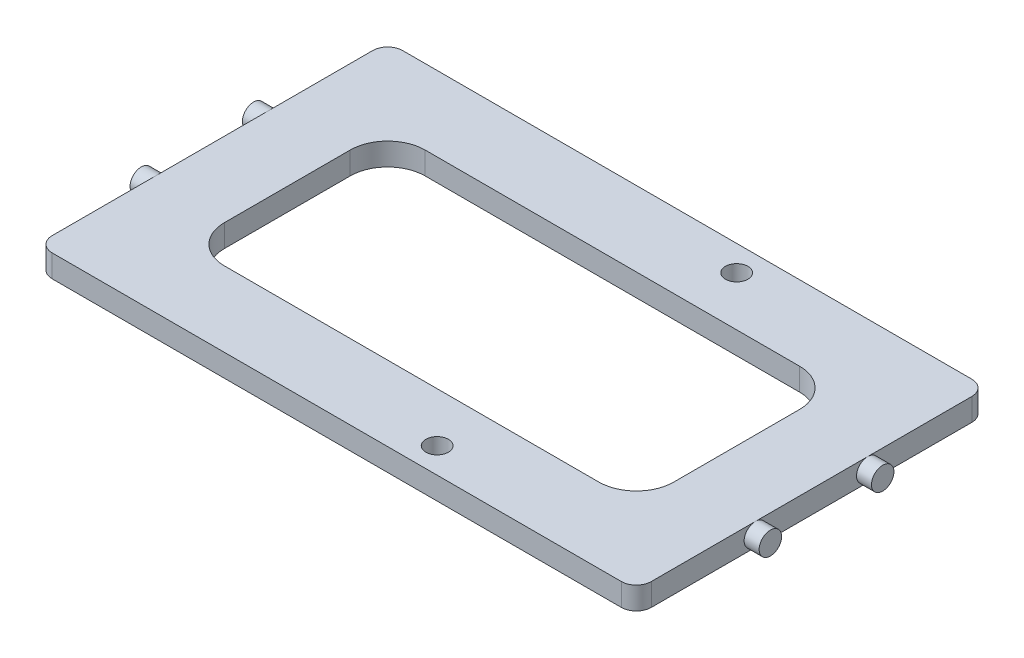
SolidWorks part; units mm, degrees
material "Copper"
ref_plane "Front Plane" through (0, 0, 0) normal (0, 0, 1) x (1, 0, 0)
ref_plane "Top Plane" through (0, 0, 0) normal (0, 1, 0) x (1, 0, 0)
ref_plane "Right Plane" through (0, 0, 0) normal (1, 0, 0) x (0, 0, -1)
sketch "Sketch1" plane through (0, 0, 0) normal (0, 1, 0) x (1, 0, 0)
  line L1 (0, 0) -> (101.6, 0)
  line L2 (0, 0) -> (0, 59.436)
  line L3 (0, 59.436) -> (101.6, 59.436)
  line L4 (101.6, 0) -> (101.6, 59.436)
  dimension "D1" = 59.436
  dimension "D2" = 101.6
extrude "Base Extrude" add sketch "Sketch1" along normal blind 3.81
fillet "Base Corner Fillet" radius 2.54 4 edges at (0, 1.905, 0) (0, 1.905, -59.436) (101.6, 1.905, -59.436) (101.6, 1.905, 0)
sketch "Sketch3" plane through (0, 0, 0) normal (-1, 0, 0) x (0, 0, 1)
  line L0 (-29.718, 3.81) -> (-29.718, 0) construction
  line L1 (-56.896, 3.81) -> (-2.54, 3.81) construction
  line L2 (-56.896, 0) -> (-2.54, 0) construction
  line L3 (0, 1.905) -> (-59.436, 1.905) construction
  line L4 (0, 3.81) -> (0, 0) construction
  line L5 (-59.436, 0) -> (-59.436, 3.81) construction
  circle A0 centre (-20.193, 1.905) radius 1.905
  circle A1 centre (-39.243, 1.905) radius 1.905
  dimension "D1" = 3.81
  dimension "D2" = 9.525
extrude "Peg Extrude" add sketch "Sketch3" along normal blind 2.54
ref_plane "Peg Mirror Plane" through (50.8, 0, 0) normal (1, 0, 0) x (0, 0, -1)
mirror "Peg Mirror" about plane through (50.8, 0, 0) normal (1, 0, 0) of "Peg Extrude"
sketch "Sketch4" plane through (0, 0, 0) normal (0, -1, 0) x (1, 0, 0)
  line L0 (2.54, 0) -> (99.06, 0) construction
  line L1 (19.05, -12.7) -> (82.55, -12.7)
  line L2 (12.7, -19.05) -> (12.7, -40.386)
  line L3 (19.05, -46.736) -> (82.55, -46.736)
  line L4 (88.9, -19.05) -> (88.9, -40.386)
  line L5 (99.06, -59.436) -> (2.54, -59.436) construction
  line L6 (0, -39.243) -> (0, -20.193) construction
  line L7 (101.6, -20.193) -> (101.6, -39.243) construction
  arc A0 (82.55, -12.7) -> (88.9, -19.05) centre (82.55, -19.05) cw
  arc A1 (82.55, -46.736) -> (88.9, -40.386) centre (82.55, -40.386) ccw
  arc A2 (12.7, -40.386) -> (19.05, -46.736) centre (19.05, -40.386) ccw
  arc A3 (19.05, -12.7) -> (12.7, -19.05) centre (19.05, -19.05) ccw
  dimension "D5" = 6.35
  dimension "D1" = 12.7
  dimension "D2" = 12.7
  dimension "D3" = 12.7
  dimension "D4" = 12.7
extrude "Material Removal Cut" cut sketch "Sketch4" against normal through all
sketch "Sketch5" plane through (0, 3.81, 0) normal (0, 1, 0) x (1, 0, 0)
  line L0 (0, 29.718) -> (101.6, 29.718) construction
  line L1 (0, 39.243) -> (0, 20.193) construction
  line L2 (101.6, 20.193) -> (101.6, 39.243) construction
  line L3 (63.5, 55.118) -> (63.5, 4.318) construction
  circle A0 centre (63.5, 4.318) radius 1.905
  circle A1 centre (63.5, 55.118) radius 1.905
  point P4 (63.5, 29.718)
  dimension "D1" = 3.81
  dimension "D2" = 50.8
  dimension "D3" = 63.5
extrude "Remote Control Holder Cut" cut sketch "Sketch5" against normal through all
